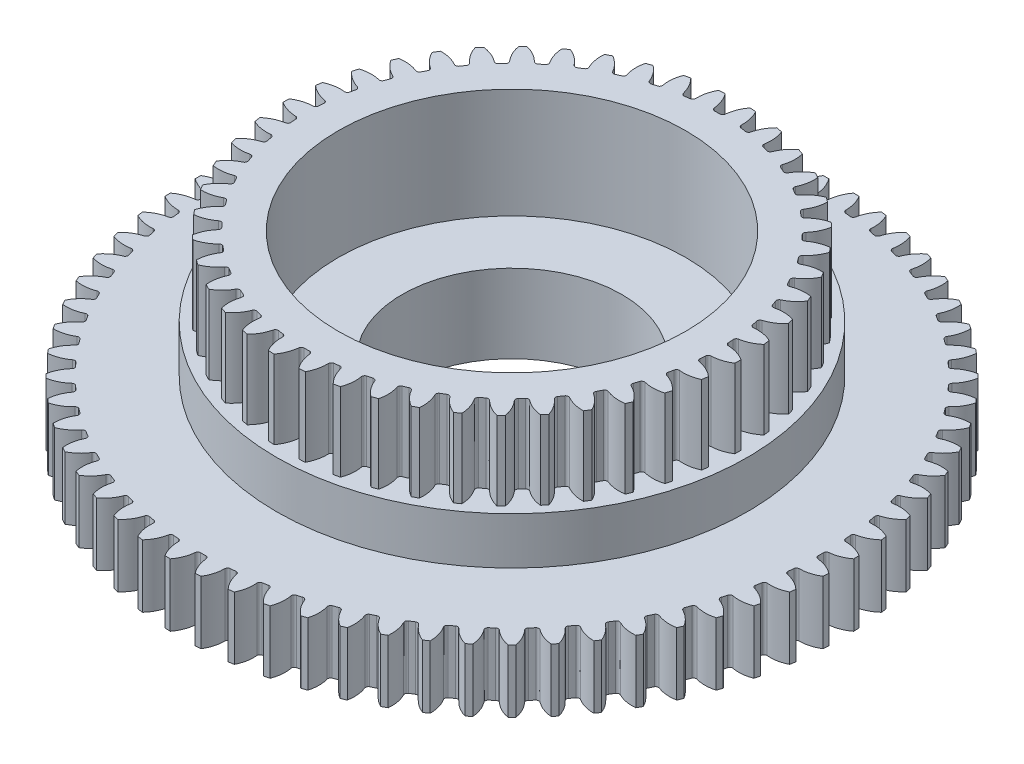
SolidWorks part; units mm, degrees
ref_plane "Ebene vorne" through (0, 0, 0) normal (0, 0, 1) x (1, 0, 0)
ref_plane "Ebene oben" through (0, 0, 0) normal (0, 1, 0) x (1, 0, 0)
ref_plane "Ebene rechts" through (0, 0, 0) normal (1, 0, 0) x (0, 0, -1)
sketch "Skizze1" plane through (0, 0, 0) normal (0, 1, 0) x (1, 0, 0)
  circle A0 centre (0, 0) radius 7
  circle A1 centre (0, 0) radius 15
  dimension "D1" = 14
  dimension "D2" = 30
extrude "Aufsatz-Linear austragen1" add sketch "Skizze1" along normal blind 1
sketch "Skizze2" plane through (0, 1, 0) normal (0, 1, 0) x (1, 0, 0)
  circle A0 centre (0, 0) radius 11.075
  circle A1 centre (0, 0) radius 15
  dimension "D1" = 30
  dimension "D2" = 22.15
extrude "Aufsatz-Linear austragen2" add sketch "Skizze2" along normal blind 2
sketch "Skizze3" plane through (0, 0, 0) normal (0, -1, 0) x (1, 0, 0)
  circle A0 centre (0, 0) radius 7
  circle A1 centre (0, 0) radius 20.4 construction
  circle A2 centre (0, 0) radius 21
  dimension "D3" = 0.6
  dimension "D1" = 14
  dimension "D2" = 40.8
extrude "Aufsatz-Linear austragen3" add sketch "Skizze3" along normal blind 4
sketch "Skizze4" plane through (0, 3, 0) normal (0, 1, 0) x (1, 0, 0)
  circle A0 centre (0, 0) radius 11.075
  circle A1 centre (0, 0) radius 13.8 construction
  circle A2 centre (0, 0) radius 14.4
  dimension "D1" = 22.15
  dimension "D2" = 27.6
  dimension "D3" = 0.6
extrude "Aufsatz-Linear austragen4" add sketch "Skizze4" along normal blind 5
sketch "Skizze8" plane through (0, 8, 0) normal (0, 1, 0) x (1, 0, 0)
  line L0 (0, 0) -> (0, 13.8) construction
  line L1 (0, 0) -> (-0.3354, 13.0757) construction
  line L2 (-0.4711, 13.792) -> (0.4711, 13.792) construction
  line L3 (0, 12.4975) -> (-0.6865, 14.3836) construction
  line L4 (0.4711, 13.792) -> (1.4112, 13.7277) construction
  line L5 (0, 0) -> (0.9827, 14.3664) construction
  circle A0 centre (0, 0) radius 13.8 construction
  arc A1 (-0.7892, 14.3784) -> (-0.3354, 13.0757) centre (-2.5985, 13.0177) cw
  arc A2 (0.7892, 14.3784) -> (0.3354, 13.0757) centre (2.5985, 13.0177) ccw
  arc A3 (-0.3354, 13.0757) -> (0.3354, 13.0757) centre (0, 0) cw
  arc A4 (0.7892, 14.3784) -> (-0.7892, 14.3784) centre (0, 0) ccw
  circle A5 centre (0, 0) radius 14.4 construction
  dimension "D1" = 27.6
  dimension "D2" = 14.4
  dimension "D4" = 13.08
  dimension "D3" = 20
  dimension "D5" = 3.913
extrude "Schnitt-Linear austragen1" cut sketch "Skizze8" against normal blind 5
fillet "Verrundung1" radius 0.18 2 edges at (-0.3354, 5.5, -13.0757) (0.3354, 5.5, -13.0757)
pattern_circular "Kreismuster1" count 46 over 360 about axis through (0, 8, 0) along (0, -1, 0) of "Verrundung1", "Schnitt-Linear austragen1" reverse direction yes
sketch "Skizze9" plane through (0, -4, 0) normal (0, -1, 0) x (1, 0, 0)
  line L0 (0, 0) -> (0, 21) construction
  line L1 (0, 0) -> (-0.3383, 19.6771) construction
  line L2 (0, 0) -> (0.9699, 20.9776) construction
  line L3 (-0.4712, 20.3946) -> (0.4712, 20.3946) construction
  line L4 (0.4712, 20.3946) -> (1.4126, 20.351) construction
  line L5 (0, 19.1) -> (-0.6875, 20.9887) construction
  circle A0 centre (0, 0) radius 21
  circle A1 centre (0, 0) radius 20.4 construction
  circle A2 centre (0, 0) radius 19.68
  arc A3 (-0.7954, 20.9849) -> (-0.3383, 19.6771) centre (-2.5467, 19.6391) cw
  arc A4 (0.7954, 20.9849) -> (0.3383, 19.6771) centre (2.5467, 19.6391) ccw
  dimension "D2" = 40.8
  dimension "D1" = 42
  dimension "D3" = 39.36
  dimension "D4" = 2.647
  dimension "D5" = 20
extrude "Schnitt-Linear austragen2" cut sketch "Skizze9" against normal up to surface (4 mm away) contours A4 A0 A3 A2 region at (0, -4, 20.4385) up to face at (0, 0, 15)
fillet "Verrundung2" radius 0.18 2 edges at (-0.3383, -2, 19.6771) (0.3383, -2, 19.6771)
pattern_circular "Kreismuster2" count 68 over 360 about axis through (0, -4, 0) along (0, 1, 0) of "Verrundung2", "Schnitt-Linear austragen2"
equation "\"Tooth1\"= 46"
equation "\"Tooth2\"= 68"
equation "\"Module\"= 0.6mm"
equation "\"D2@Skizze4\"=\"Tooth1\"*\"Module\""
equation "\"D4@Skizze8\"=(\"Module\"*\"Tooth1\"- (\"Module\"*if(\"Module\" => 1.25,2.25,2.4)))/2"
equation "\"D5@Skizze8\"=180/\"Tooth1\""
equation "\"D3@Skizze4\"=\"Module\""
equation "\"D1@Verrundung1\"=0.3*\"Module\""
equation "\"D1@Kreismuster1\"=\"Tooth1\""
equation "\"D2@Skizze3\"=\"Tooth2\"*\"Module\""
equation "\"D3@Skizze3\"=\"Module\""
equation "\"D1@Skizze8\"=\"Tooth1\"*\"Module\""
equation "\"D1@Skizze9\"=(\"Tooth2\"+2)*\"Module\""
equation "\"D2@Skizze9\"=\"Tooth2\"*\"Module\""
equation "\"D3@Skizze9\"=(\"Module\"*\"Tooth2\"- (\"Module\"*if(\"Module\" => 1.25,2.25,2.4)))"
equation "\"D4@Skizze9\"=180/\"Tooth2\""
equation "\"D1@Verrundung2\"=0.3*\"Module\""
equation "\"D1@Kreismuster2\"=\"Tooth2\""
equation "\"D2@Skizze8\"=((2+\"Tooth1\")*\"Module\")/2"
